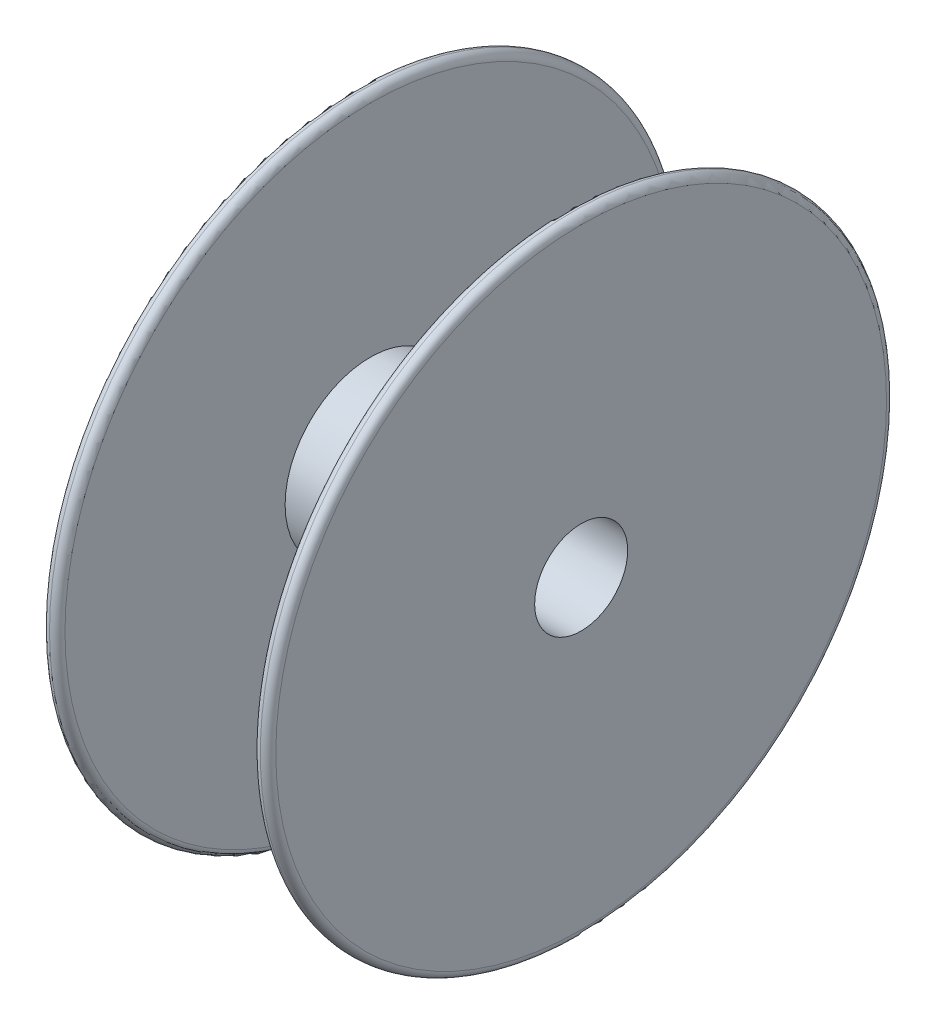
SolidWorks part; units mm, degrees
ref_plane "Front Plane" through (0, 0, 0) normal (0, 0, 1) x (1, 0, 0)
ref_plane "Top Plane" through (0, 0, 0) normal (0, 1, 0) x (1, 0, 0)
ref_plane "Right Plane" through (0, 0, 0) normal (1, 0, 0) x (0, 0, -1)
sketch "Sketch1" plane through (0, 0, 0) normal (1, 0, 0) x (0, 0, -1)
  circle A0 centre (0, 0) radius 15
  circle A1 centre (0, 0) radius 27.5
  dimension "D1" = 30
  dimension "D2" = 55
extrude "Boss-Extrude1" add sketch "Sketch1" along normal blind 63
sketch "Sketch2" plane through (63, 0, 0) normal (1, 0, 0) x (0, 0, -1)
  circle A0 centre (0, 0) radius 101
  circle A1 centre (0, 0) radius 15 construction
  circle A2 centre (0, 0) radius 15
  dimension "D1" = 202
extrude "Boss-Extrude2" add sketch "Sketch2" along normal blind 5
sketch "Sketch3" plane through (0, 0, 0) normal (-1, 0, 0) x (0, 0, 1)
  circle A0 centre (0, 0) radius 15 construction
  circle A1 centre (0, 0) radius 15
  circle A2 centre (0, 0) radius 101
  dimension "D1" = 202
extrude "Boss-Extrude3" add sketch "Sketch3" along normal blind 5
fillet "Fillet1" radius 2.5 4 edges at (-5, 0, 101) (0, 0, 101) (63, 0, -101) (68, 0, -101)
